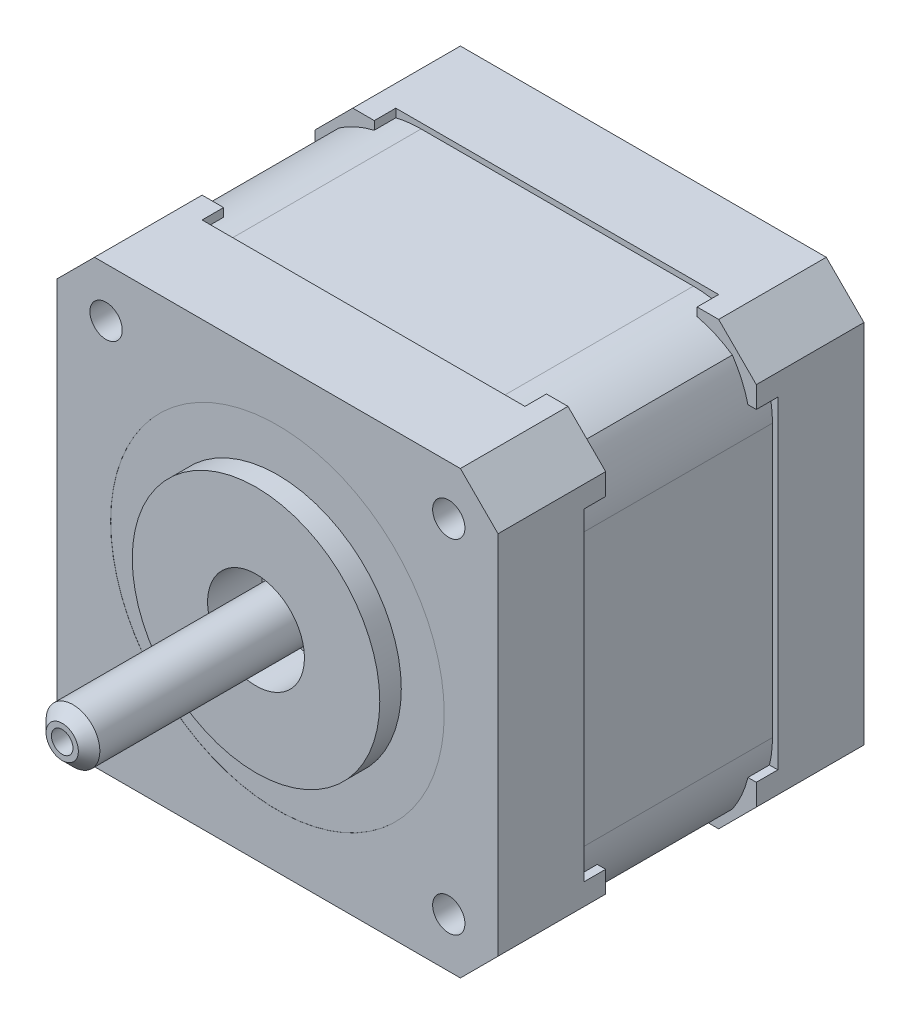
SolidWorks part; units mm, degrees
ref_plane "Ön Düzlem" through (0, 0, 0) normal (0, 0, 1) x (1, 0, 0)
ref_plane "Üst Düzlem" through (0, 0, 0) normal (0, 1, 0) x (1, 0, 0)
ref_plane "Sağ Düzlem" through (0, 0, 0) normal (1, 0, 0) x (0, 0, -1)
sketch "Çizim1" plane through (0, 0, 0) normal (0, 0, 1) x (1, 0, 0)
  line L3 (-17, 41) -> (17, 41)
  line L4 (20.5, 3.5) -> (20.5, 37.5)
  line L5 (-20.5, 3.5) -> (-20.5, 37.5)
  line L6 (17, 41) -> (20.5, 37.5)
  line L7 (-17, 41) -> (-20.5, 37.5)
  line L8 (17, 0) -> (20.5, 3.5)
  line L9 (-17, 0) -> (-20.5, 3.5)
  line L10 (-17, 0) -> (17, 0)
extrude "Yükseklik-Ekstrüzyon2" add sketch "Çizim1" along normal blind 8
sketch "Çizim5" plane through (0, 0, 0) normal (0, 0, -1) x (-1, 0, 0)
  line L0 (-20.5, 3.5) -> (-20.5, 5.5)
  line L1 (-20.5, 3.5) -> (-20.5, 37.5) construction
  line L2 (-20.5, 5.5) -> (-20, 5.5)
  line L3 (-17, 0) -> (-15, 0)
  line L4 (17, 0) -> (-17, 0) construction
  line L5 (-15, 0) -> (-15, 0.5)
  line L6 (20.5, 20.5) -> (10.3627, 20.5)
  line L7 (15, 0) -> (15, 0.5)
  line L8 (-20, 3.7071) -> (-20, 37.2929)
  line L9 (-20, 37.2929) -> (-16.7929, 40.5)
  line L10 (-16.7929, 40.5) -> (16.7929, 40.5)
  line L11 (16.7929, 40.5) -> (20, 37.2929)
  line L12 (20, 37.2929) -> (20, 3.7071)
  line L13 (20, 3.7071) -> (16.7929, 0.5)
  line L14 (16.7929, 0.5) -> (-16.7929, 0.5)
  line L15 (-16.7929, 0.5) -> (-20, 3.7071)
  line L16 (17, 0) -> (15, 0)
  line L17 (20.5, 5.5) -> (20, 5.5)
  line L18 (20.5, 3.5) -> (20.5, 5.5)
  line L19 (20.5, 37.5) -> (20.5, 3.5) construction
  line L20 (-20.5, 35.5) -> (-20, 35.5)
  line L21 (-15, 41) -> (-15, 40.5)
  line L22 (15, 41) -> (15, 40.5)
  line L23 (20.5, 37.5) -> (20.5, 35.5)
  line L24 (20.5, 35.5) -> (20, 35.5)
  line M4 (20.5, 37.5) -> (17, 41)
  line M5 (17, 41) -> (-17, 41)
  line M6 (-17, 41) -> (-20.5, 37.5)
  line M7 (-20.5, 37.5) -> (-20.5, 3.5)
  line M8 (-20.5, 3.5) -> (-17, 0)
  line M9 (-17, 0) -> (17, 0)
  line M10 (17, 0) -> (20.5, 3.5)
  line M11 (20.5, 3.5) -> (20.5, 37.5)
extrude "Yükseklik-Ekstrüzyon10" add sketch "Çizim5" along normal blind 2 contours L21 L20 L8 L9 L10 M5 M6 M7 | L24 L22 L10 L11 L12 M11 M4 M5 | L17 L12 L13 L14 L7 M11 M9 M10 | L14 L15 L8 L2 L5 M7 M8 M9 region at (20.4222, 4.5, 0) region at (20.4222, 36.5, 0) region at (-15.0778, 0.25, 0) region at (-16, 40.9222, 0)
sketch "Çizim12" plane through (0, 0, 0) normal (0, 0, -1) x (-1, 0, 0)
  line L1 (-20.5, 5.5) -> (-20.5, 3.5)
  line L2 (-20.5, 3.5) -> (-17, 0)
  line L3 (-17, 0) -> (17, 0)
  line L4 (17, 0) -> (20.5, 3.5)
  line L5 (20.5, 3.5) -> (20.5, 37.5)
  line L6 (20.5, 37.5) -> (17, 41)
  line L7 (17, 41) -> (-17, 41)
  line L8 (-17, 41) -> (-20.5, 37.5)
  line L9 (-20.5, 37.5) -> (-20.5, 35.5)
  line L10 (-20.5, 35.5) -> (-20.4853, 35.5072)
  line L11 (-20, 35.5) -> (-20, 5.5)
  line L12 (-20, 5.5) -> (-20, 3.7071)
  line L13 (-20, 3.7071) -> (-16.7929, 0.5)
  line L14 (-16.7929, 0.5) -> (16.7929, 0.5)
  line L15 (16.7929, 0.5) -> (20, 3.7071)
  line L16 (20, 3.7071) -> (20, 37.2929)
  line L17 (20, 37.2929) -> (16.7929, 40.5)
  line L18 (16.7929, 40.5) -> (-16.7929, 40.5)
  line L19 (-16.7929, 40.5) -> (-20, 37.2929)
  line L20 (-20, 37.2929) -> (-20, 35.5)
  line L21 (-20.5, 35.5) -> (-20.5, 5.5) construction
  line M3 (-20, 5.5) -> (-20, 3.7071)
  line M4 (-20, 3.7071) -> (-16.7929, 0.5)
  line M5 (-16.7929, 0.5) -> (-15, 0.5)
  line M9 (15, 0.5) -> (16.7929, 0.5)
  line M10 (16.7929, 0.5) -> (20, 3.7071)
  line M11 (20, 3.7071) -> (20, 5.5)
  line M15 (20, 35.5) -> (20, 37.2929)
  line M16 (20, 37.2929) -> (16.7929, 40.5)
  line M17 (16.7929, 40.5) -> (15, 40.5)
  line M21 (-15, 40.5) -> (-16.7929, 40.5)
  line M22 (-16.7929, 40.5) -> (-20, 37.2929)
  line M23 (-20, 37.2929) -> (-20, 35.5)
  dimension "D1" = 0.5
extrude "Yükseklik-Ekstrüzyon11" add sketch "Çizim12" along normal blind 18 contours L18 L11 L14 L16 M17 M21 M22 M23 M3 M4 M5 M9 M10 M11 M15 M16 region at (0, 20.5, 0)
sketch "Çizim13" plane through (0, 0, -18) normal (0, 0, -1) x (-1, 0, 0)
  line L0 (-17, 41) -> (-20.5, 37.5)
  line L1 (-20.5, 37.5) -> (-20.5, 3.5)
  line L2 (-20.5, 3.5) -> (-17, 0)
  line L3 (-17, 0) -> (17, 0)
  line L4 (17, 0) -> (20.5, 3.5)
  line L5 (20.5, 3.5) -> (20.5, 37.5)
  line L6 (20.5, 37.5) -> (17, 41)
  line L7 (17, 41) -> (-17, 41)
extrude "Yükseklik-Ekstrüzyon12" add sketch "Çizim13" along normal blind 8
sketch "Çizim14" plane through (0, 0, -18) normal (0, 0, 1) x (1, 0, 0)
  line L0 (17, 41) -> (15, 41)
  line L1 (-17, 41) -> (17, 41) construction
  line L2 (15, 41) -> (15, 40.5)
  line L3 (-16.7929, 40.5) -> (16.7929, 40.5) construction
  line L4 (15, 40.5) -> (16.7929, 40.5)
  line L5 (16.7929, 40.5) -> (20, 37.2929)
  line L6 (20.5, 37.5) -> (20.5, 35.5)
  line L7 (20.5, 37.5) -> (20.5, 3.5) construction
  line L8 (20.5, 35.5) -> (20, 35.5)
  line L9 (20, 37.2929) -> (20, 3.7071) construction
  line L10 (20, 35.5) -> (20, 37.2929)
  line L11 (20.5, 37.5) -> (17, 41)
  line L12 (0, 0) -> (0, 15.5815)
  line L13 (17, 0) -> (15, 0)
  line L14 (15, 0) -> (15, 0.5)
  line L15 (15, 0.5) -> (16.7929, 0.5)
  line L16 (20.5, 3.5) -> (17, 0)
  line L17 (16.7929, 0.5) -> (20, 3.7071)
  line L18 (20, 5.5) -> (20, 3.7071)
  line L19 (20.5, 3.5) -> (20.5, 5.5)
  line L20 (20.5, 5.5) -> (20, 5.5)
  line L21 (-20.5, 5.5) -> (-20, 5.5)
  line L22 (-20.5, 3.5) -> (-20.5, 5.5)
  line L23 (-20, 5.5) -> (-20, 3.7071)
  line L24 (-20.5, 3.5) -> (-17, 0)
  line L25 (-16.7929, 0.5) -> (-20, 3.7071)
  line L26 (-15, 0.5) -> (-16.7929, 0.5)
  line L27 (-15, 0) -> (-15, 0.5)
  line L28 (-17, 0) -> (-15, 0)
  line L29 (-20.5, 35.5) -> (-20, 35.5)
  line L30 (-20, 35.5) -> (-20, 37.2929)
  line L31 (-20.5, 37.5) -> (-20.5, 35.5)
  line L32 (-20.5, 37.5) -> (-17, 41)
  line L33 (-16.7929, 40.5) -> (-20, 37.2929)
  line L34 (-15, 40.5) -> (-16.7929, 40.5)
  line L35 (-17, 41) -> (-15, 41)
  line L36 (-15, 41) -> (-15, 40.5)
  line M19 (17, 41) -> (-17, 41)
  line M20 (-17, 41) -> (-20.5, 37.5)
  line M21 (-20.5, 37.5) -> (-20.5, 3.5)
  line M22 (-20.5, 3.5) -> (-17, 0)
  line M23 (-17, 0) -> (17, 0)
  line M24 (17, 0) -> (20.5, 3.5)
  line M25 (20.5, 3.5) -> (20.5, 37.5)
  line M26 (20.5, 37.5) -> (17, 41)
  line M27 (20, 37.2929) -> (20, 3.7071)
  line M28 (20, 3.7071) -> (16.7929, 0.5)
  line M29 (16.7929, 0.5) -> (-16.7929, 0.5)
  line M30 (-16.7929, 0.5) -> (-20, 3.7071)
  line M31 (-20, 3.7071) -> (-20, 37.2929)
  line M32 (-20, 37.2929) -> (-16.7929, 40.5)
  line M33 (-16.7929, 40.5) -> (16.7929, 40.5)
  line M34 (16.7929, 40.5) -> (20, 37.2929)
extrude "Yükseklik-Ekstrüzyon14" add sketch "Çizim14" along normal blind 2 contours L36 L29 M19 M20 M21 M31 M32 M33 | L27 L21 M23 M29 M30 M31 M21 M22 | L20 L14 M25 M27 M28 M29 M23 M24 | L8 L2 M25 M26 M19 M33 M34 M27 region at (18.695, 39.195, -18) region at (-15.0778, 40.75, -18) region at (20.4222, 4.5, -18) region at (-20.25, 5.4222, -18)
fillet "Radyus5" radius 10 8 edges at (-16.7929, 0.5, -9) (-20, 3.7071, -9) (-20, 37.2929, -9) (-16.7929, 40.5, -9) (16.7929, 40.5, -9) (20, 37.2929, -9) (20, 3.7071, -9) (16.7929, 0.5, -9)
sketch "Çizim15" plane through (0, 0, -26) normal (0, 0, -1) x (-1, 0, 0)
  circle A0 centre (0, 20.5) radius 4.5
extrude "Kes-Ekstrüzyon3" cut sketch "Çizim15" against normal blind 3
fillet "Radyus6" radius 0.5 1 edges at (-4.5, 20.5, -26)
sketch "Çizim16" plane through (0, 0, -23) normal (0, 0, -1) x (-1, 0, 0)
  circle A0 centre (0, 20.5) radius 3
extrude "Yükseklik-Ekstrüzyon15" add sketch "Çizim16" along normal blind 1
fillet "Radyus7" radius 0.5 1 edges at (-3, 20.5, -24)
sketch "Çizim17" plane through (0, 0, -24) normal (0, 0, -1) x (-1, 0, 0)
  line L1 (1.2603, 19.7965) -> (1.2394, 21.2397)
  line L2 (1.2394, 21.2397) -> (-0.0209, 21.9432)
  line L3 (-0.0209, 21.9432) -> (-1.2603, 21.2035)
  line L4 (-1.2603, 21.2035) -> (-1.2394, 19.7603)
  line L5 (-1.2394, 19.7603) -> (0.0209, 19.0568)
  line L6 (0.0209, 19.0568) -> (1.2603, 19.7965)
  circle A0 centre (0, 20.5) radius 1.25 construction
extrude "Kes-Ekstrüzyon4" cut sketch "Çizim17" against normal blind 0.5
sketch "Çizim18" plane through (0, 0, -26) normal (0, 0, -1) x (-1, 0, 0)
  line L0 (0, 20.5) -> (0, 35.5)
  line L1 (0, 20.5) -> (15, 20.5)
  line L2 (0, 35.5) -> (15, 35.5)
  line L3 (15, 35.5) -> (15, 20.5)
  circle A0 centre (15, 35.5) radius 3
  circle A1 centre (15, 5.5) radius 3
  circle A2 centre (-15, 5.5) radius 3
  circle A3 centre (-15, 35.5) radius 3
extrude "Kes-Ekstrüzyon5" cut sketch "Çizim18" against normal blind 1 contours A2 | A0 | A1 | A3 region at (15, 5.5, -26)
sketch "Çizim19" plane through (0, 0, -25) normal (0, 0, -1) x (-1, 0, 0)
  circle A0 centre (15, 35.5) radius 2
  circle A1 centre (15, 5.5) radius 2
  circle A2 centre (-15, 5.5) radius 2
  circle A3 centre (-15, 35.5) radius 2
extrude "Yükseklik-Ekstrüzyon17" add sketch "Çizim19" along normal blind 0.5
fillet "Radyus8" radius 0.5 4 edges at (13, 5.5, -25.5) (-13, 5.5, -25.5) (-17, 35.5, -25.5) (17, 35.5, -25.5)
sketch "Çizim21" plane through (0, 0, -25.5) normal (0, 0, -1) x (-1, 0, 0)
  line L0 (0, 20.5) -> (9.2525, 20.5)
  line L1 (9.2525, 20.5) -> (0, 20.5)
  line L2 (0, 20.5) -> (0, 30.2455)
  line L3 (15.15, 6.5) -> (14.85, 6.5)
  line L4 (15.15, 35.65) -> (15.15, 36.5)
  line L5 (15.15, 35.35) -> (16, 35.35)
  line L6 (14.85, 35.35) -> (14.85, 34.5)
  line L7 (14.85, 35.65) -> (14, 35.65)
  line L8 (14.85, 35.65) -> (14.85, 36.5)
  line L9 (15.15, 35.65) -> (16, 35.65)
  line L10 (15.15, 35.35) -> (15.15, 34.5)
  line L11 (14.85, 35.35) -> (14, 35.35)
  line L12 (14.85, 36.5) -> (15.15, 36.5)
  line L13 (16, 35.65) -> (16, 35.35)
  line L14 (15.15, 34.5) -> (14.85, 34.5)
  line L15 (14, 35.35) -> (14, 35.65)
  line L16 (14, 35.65) -> (14.0342, 35.6422)
  line L17 (14, 5.35) -> (14.0342, 5.3578)
  line L18 (14, 5.65) -> (14, 5.35)
  line L19 (16, 5.35) -> (16, 5.65)
  line L20 (14.85, 5.65) -> (14, 5.65)
  line L21 (15.15, 5.65) -> (15.15, 6.5)
  line L22 (15.15, 5.35) -> (16, 5.35)
  line L23 (14.85, 5.35) -> (14, 5.35)
  line L24 (14.85, 5.65) -> (14.85, 6.5)
  line L25 (15.15, 5.65) -> (16, 5.65)
  line L26 (14.85, 4.5) -> (15.15, 4.5)
  line L27 (14.85, 5.35) -> (14.85, 4.5)
  line L28 (15.15, 5.35) -> (15.15, 4.5)
  line L29 (-14, 35.65) -> (-14.0342, 35.6422)
  line L30 (-14, 35.35) -> (-14, 35.65)
  line L31 (-14.85, 36.5) -> (-15.15, 36.5)
  line L32 (-15.15, 34.5) -> (-14.85, 34.5)
  line L33 (-16, 35.65) -> (-16, 35.35)
  line L34 (-14.85, 35.35) -> (-14, 35.35)
  line L35 (-15.15, 35.35) -> (-15.15, 34.5)
  line L36 (-15.15, 35.65) -> (-16, 35.65)
  line L37 (-14.85, 35.65) -> (-14.85, 36.5)
  line L38 (-14.85, 35.65) -> (-14, 35.65)
  line L39 (-14.85, 35.35) -> (-14.85, 34.5)
  line L40 (-15.15, 35.35) -> (-16, 35.35)
  line L41 (-15.15, 35.65) -> (-15.15, 36.5)
  line L42 (-16, 5.35) -> (-16, 5.65)
  line L43 (-15.15, 5.35) -> (-15.15, 4.5)
  line L44 (-14.85, 5.35) -> (-14.85, 4.5)
  line L45 (-14.85, 4.5) -> (-15.15, 4.5)
  line L46 (-15.15, 5.65) -> (-16, 5.65)
  line L47 (-14.85, 5.65) -> (-14.85, 6.5)
  line L48 (-14.85, 5.35) -> (-14, 5.35)
  line L49 (-15.15, 5.35) -> (-16, 5.35)
  line L50 (-15.15, 5.65) -> (-15.15, 6.5)
  line L51 (-14.85, 5.65) -> (-14, 5.65)
  line L52 (-14, 5.65) -> (-14, 5.35)
  line L53 (-14, 5.35) -> (-14.0342, 5.3578)
  line L54 (-15.15, 6.5) -> (-14.85, 6.5)
  point P0 (15, 35.5)
  point P1 (15, 36.5)
  point P3 (15.15, 35.5)
  point P4 (16, 35.5)
  point P5 (15, 34.5)
  point P10 (14.85, 35.5)
  point P14 (14.85, 35.5)
extrude "Kes-Ekstrüzyon6" cut sketch "Çizim21" against normal blind 0.1 contours L41 L36 L33 L40 L35 L32 L39 L34 L30 L38 L37 L31 | L15 L11 L6 L14 L10 L5 L13 L9 L4 L12 L8 L7 | L28 L22 L19 L25 L21 L3 L24 L20 L18 L23 L27 L26 | L54 L50 L46 L42 L49 L43 L45 L44 L48 L52 L51 L47 region at (-15, 5.5, -25.5) region at (-15, 35.5, -25.5) region at (15, 35.5, -25.5) region at (15, 5.5, -25.5)
sketch "Çizim22" plane through (0, 0, 8) normal (0, 0, 1) x (1, 0, 0)
  circle A0 centre (0, 20.5) radius 4.5
extrude "Kes-Ekstrüzyon7" cut sketch "Çizim22" against normal blind 3
sketch "Çizim23" plane through (0, 0, 5) normal (0, 0, 1) x (1, 0, 0)
  circle A0 centre (0, 20.5) radius 2.5
extrude "Yükseklik-Ekstrüzyon18" add sketch "Çizim23" along normal blind 23
sketch "Çizim24" plane through (0, 0, 28) normal (0, 0, 1) x (1, 0, 0)
  circle A0 centre (0, 20.5) radius 1
extrude "Kes-Ekstrüzyon8" cut sketch "Çizim24" against normal blind 2
chamfer "Pah1" distance 1 angle 45 1 edges at (2.5, 20.5, 28)
sketch "Çizim25" plane through (0, 0, 8) normal (0, 0, 1) x (1, 0, 0)
  line L0 (20.5, 20.5) -> (15.5, 20.5)
  line L1 (20.5, 3.5) -> (20.5, 37.5) construction
  circle A0 centre (0, 20.5) radius 4.5
  circle A1 centre (0, 20.5) radius 15.5
  circle M2 centre (0, 20.5) radius 4.5
extrude "Kes-Ekstrüzyon9" cut sketch "Çizim25" against normal blind 0.01 contours A1 M2 region at (-15.0616, 20.5, 8)
sketch "Çizim26" plane through (0, 0, 7.99) normal (0, 0, 1) x (1, 0, 0)
  line L0 (15.5, 20.5) -> (11.5, 20.5)
  circle A0 centre (0, 20.5) radius 4.5
  circle A1 centre (0, 20.5) radius 15.5 construction
  circle A2 centre (0, 20.5) radius 11.5
  circle M2 centre (0, 20.5) radius 4.5
extrude "Yükseklik-Ekstrüzyon19" add sketch "Çizim26" along normal blind 2 contours A2 M2 region at (-11.1747, 20.5, 7.99)
sketch "Çizim28" plane through (0, 0, 8) normal (0, 0, 1) x (1, 0, 0)
  line L2 (0, 20.5) -> (0, 27.7903)
  line L3 (0, 27.7903) -> (0, 20.5)
  line L4 (0, 20.5) -> (6.5303, 20.5)
  circle A0 centre (-15.9216, 36.4216) radius 1.5
  circle A1 centre (15.9216, 36.4216) radius 1.5
  circle A2 centre (-15.9216, 4.5784) radius 1.5
  circle A3 centre (15.9216, 4.5784) radius 1.5
extrude "Kes-Ekstrüzyon10" cut sketch "Çizim28" against normal blind 6 contours A1 | A0 | A3 | A2 region at (-15.9216, 36.4216, 8) region at (15.9216, 36.4216, 8) region at (-15.9216, 4.5784, 8) region at (15.9216, 4.5784, 8)
